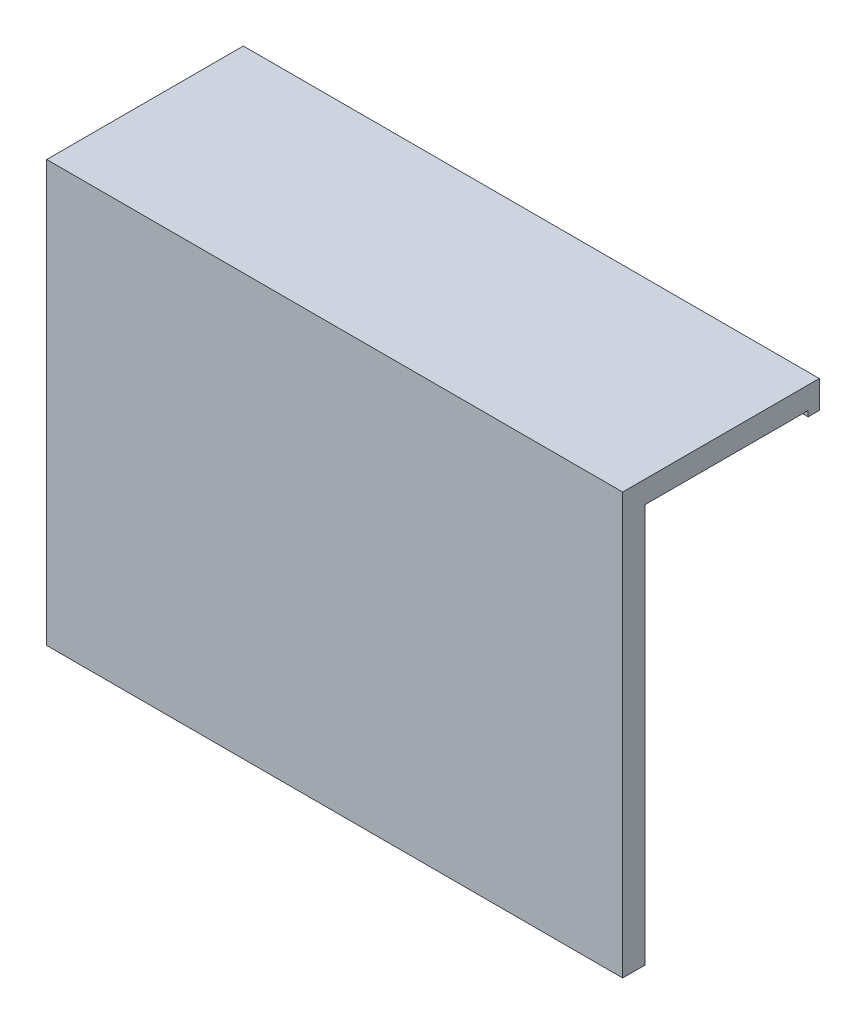
SolidWorks part; units mm, degrees
note: The reader was unsure of these and kept them because the rebuilt part matched: shared geometry of "Sketch1<3>", "Sketch6<3>".
ref_plane "Front Plane" through (0, 0, 0) normal (0, 0, 1) x (1, 0, 0)
ref_plane "Top Plane" through (0, 0, 0) normal (0, 1, 0) x (1, 0, 0)
ref_plane "Right Plane" through (0, 0, 0) normal (1, 0, 0) x (0, 0, -1)
sketch "Sketch1" plane through (0, 0, 0) normal (0, 0, 1) x (1, 0, 0)
  line L0 (-2, -2) -> (-2, 74)
  line L1 (0, 0) -> (100, 0)
  line L2 (0, 0) -> (0, 72)
  line L3 (0, 72) -> (100, 72)
  line L4 (100, 0) -> (100, 72)
  line L5 (-2, 74) -> (102, 74)
  line L6 (102, -2) -> (102, 74)
  line L7 (-2, -2) -> (102, -2)
  line L8 (100, 0) -> (102, 0)
  line L9 (0, 0) -> (-2, 0)
  dimension "D1" = 72
  dimension "D2" = 100
  dimension "D3" = 2
extrude "Boss-Extrude1" add sketch "Sketch1" along normal blind 1 contours L1 L4 L3 L2 | L0 L7 L6 L5 L4 L1 L2 L3
extrude "Boss-Extrude2" add sketch "Sketch1<3>" against normal blind 3 contours L9 L2 L3 L4 L8 L6 L5 L0
sketch "Sketch1<3>" plane through (0, 0, 0) normal (0, 0, 1) x (1, 0, 0) same geometry as "Sketch1"
sketch "Sketch2" plane through (0, 0, -3) normal (0, 0, -1) x (-1, 0, 0)
  line L0 (-102, 74) -> (2, 74)
  line L4 (2, 74) -> (2, 70)
  line L5 (2, 70) -> (0, 70)
  line L7 (0, 70) -> (0, 72)
  line L8 (0, 72) -> (-100, 72)
  line L10 (-100, 72) -> (-100, 70)
  line L12 (-100, 70) -> (-102, 70)
  line L13 (-102, 70) -> (-102, 74)
  dimension "D1" = 4
  dimension "D2" = 2
extrude "Boss-Extrude3" add sketch "Sketch2" along normal blind 29.5
sketch "Sketch3" plane through (0, 0, 0) normal (0, -1, 0) x (1, 0, 0)
  line L0 (-2, 1) -> (-2, -3) construction
  line L1 (-2, 1) -> (102, 1)
  line L2 (-2, 1) -> (-2, -3)
  line L3 (-2, -3) -> (102, -3)
  line L4 (102, 1) -> (102, -3)
  line L5 (-2, 1) -> (102, 1) construction
  line L6 (102, 1) -> (102, -3) construction
  dimension "D1" = 4
extrude "Boss-Extrude4" add sketch "Sketch3" along normal blind 2
sketch "Sketch4" plane through (-2, 0, 0) normal (-1, 0, 0) x (0, 0, 1)
  line L0 (-3, 0) -> (0, 0)
  line L2 (-3, -2) -> (-3, 70) construction
  arc A0 (0, 0) -> (-2.4, 0) centre (-1.2, 0) cw
  dimension "D2" = 1.2
  dimension "D3" = 1.2
  dimension "D1" = 3
extrude "Cut-Extrude1" cut sketch "Sketch4" against normal blind 11 and the other way blind 11 from offset 52 offset against normal yes
sketch "Sketch5" plane through (0, 0, -32.5) normal (0, 0, -1) x (-1, 0, 0)
  line L0 (-102, 74) -> (-102, 70) construction
  line L1 (-102, 74) -> (2, 74)
  line L2 (-102, 74) -> (-102, 69)
  line L3 (-102, 69) -> (2, 69)
  line L4 (2, 74) -> (2, 69)
  line L5 (2, 70) -> (2, 74) construction
  line L6 (2, 74) -> (-102, 74) construction
  dimension "D1" = 5
extrude "Boss-Extrude6" add sketch "Sketch5" along normal blind 2
sketch "Sketch6" plane through (-2, 0, 0) normal (-1, 0, 0) x (0, 0, 1)
  line L0 (-32.5, 69) -> (-32.5, 72.2)
  line L1 (-32.5, 69) -> (-32.5, 70) construction
  line L2 (-34.5, 69) -> (-32.5, 69) construction
  arc A0 (-32.5, 72.2) -> (-32.5, 69.8) centre (-32.5, 71) ccw
  dimension "D2" = 1.2
  dimension "D1" = 3.2
extrude "Cut-Extrude2" cut sketch "Sketch6" along normal blind 11 from offset 32 contours L0 A0 offset against normal yes
extrude "Cut-Extrude3" cut sketch "Sketch6<3>" against normal blind 11 from offset 72 contours L0 A0 offset against normal yes
sketch "Sketch6<3>" plane through (-2, 0, 0) normal (-1, 0, 0) x (0, 0, 1) same geometry as "Sketch6"
